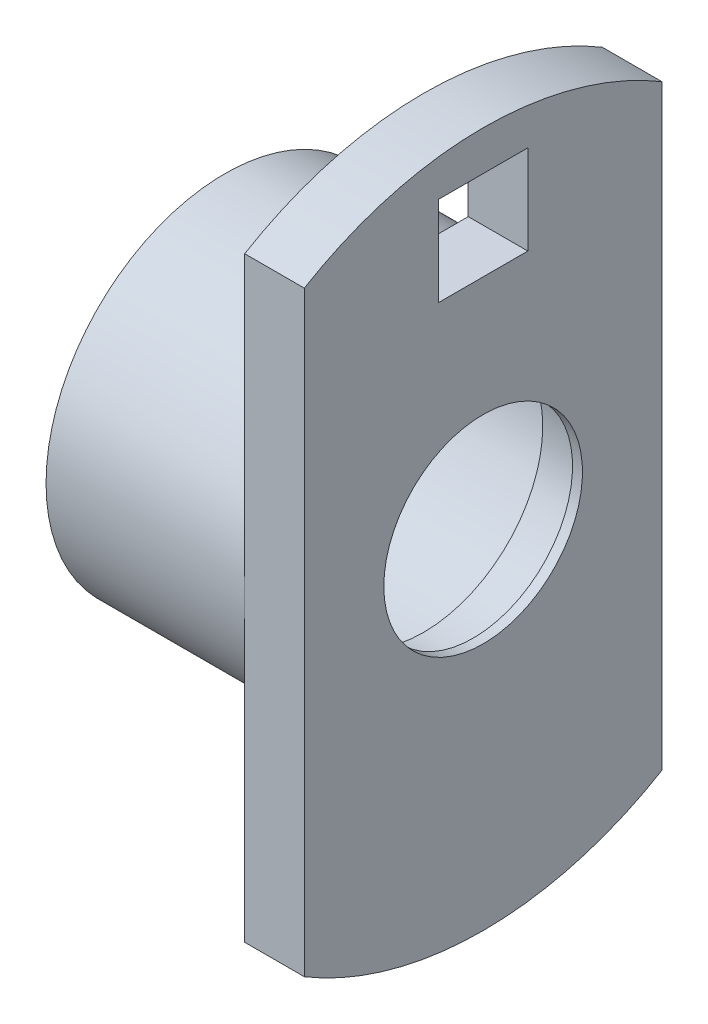
SolidWorks part; units mm, degrees
ref_plane "Front Plane" through (0, 0, 0) normal (0, 0, 1) x (1, 0, 0)
ref_plane "Top Plane" through (0, 0, 0) normal (0, 1, 0) x (1, 0, 0)
ref_plane "Right Plane" through (0, 0, 0) normal (1, 0, 0) x (0, 0, -1)
sketch "Sketch1" plane through (0, 0, 0) normal (0, 0, 1) x (1, 0, 0)
  line L0 (-42.8096, 0) -> (42.8096, 0) construction
  line L1 (-1, 12) -> (-6, 12)
  line L2 (-6, 12) -> (-6, 16)
  line L3 (-6, 16) -> (-26, 16)
  line L4 (-26, 16) -> (-26, 18)
  line L6 (0, 35) -> (0, 10)
  line L9 (0, 10) -> (-1, 10)
  line L10 (-1, 10) -> (-1, 12)
  line L11 (-26, 18) -> (-6, 18)
  line L12 (-6, 18) -> (-6, 35)
  line L13 (-6, 35) -> (0, 35)
  point P3 (0, 0)
  dimension "D1" = 2
  dimension "D2" = 6
  dimension "D3" = 5
  dimension "D4" = 24
  dimension "D5" = 32
  dimension "D6" = 2
  dimension "D7" = 70
  dimension "D8" = 6
  dimension "D9" = 20
revolve "Revolve1" add sketch "Sketch1" angle 360 about L0
sketch "Sketch2" plane through (0, 0, 0) normal (1, 0, 0) x (0, 0, -1)
  line L0 (0, 35) -> (0, 18) construction
  line L3 (0, 35) -> (0, 10) construction
  line L4 (-18, 30.0167) -> (-18, -30.0167)
  line L5 (-4.5, 22) -> (4.5, 22)
  line L6 (-4.5, 22) -> (-4.5, 31)
  line L7 (-4.5, 31) -> (4.5, 31)
  line L8 (4.5, 22) -> (4.5, 31)
  line L9 (-4.5, 22) -> (4.5, 31) construction
  line L10 (-4.5, 31) -> (4.5, 22) construction
  line L11 (18, -30.0167) -> (18, 30.0167)
  circle A0 centre (0, 0) radius 35 construction
  circle A1 centre (0, 0) radius 18 construction
  circle A3 centre (0, 0) radius 35
  point P3 (0, 26.5)
  point P5 (0, 26.5)
  dimension "D1" = 9
extrude "Cut-Extrude1" cut sketch "Sketch2" against normal up to surface (6 mm away) contours L4 A3 | L5 L8 L7 L6 | L11 A3 region at (0, 0, 24.965) region at (0, 0, -24.965) region at (0, 26.5, 0) up to face at (-6, 0, 18)
